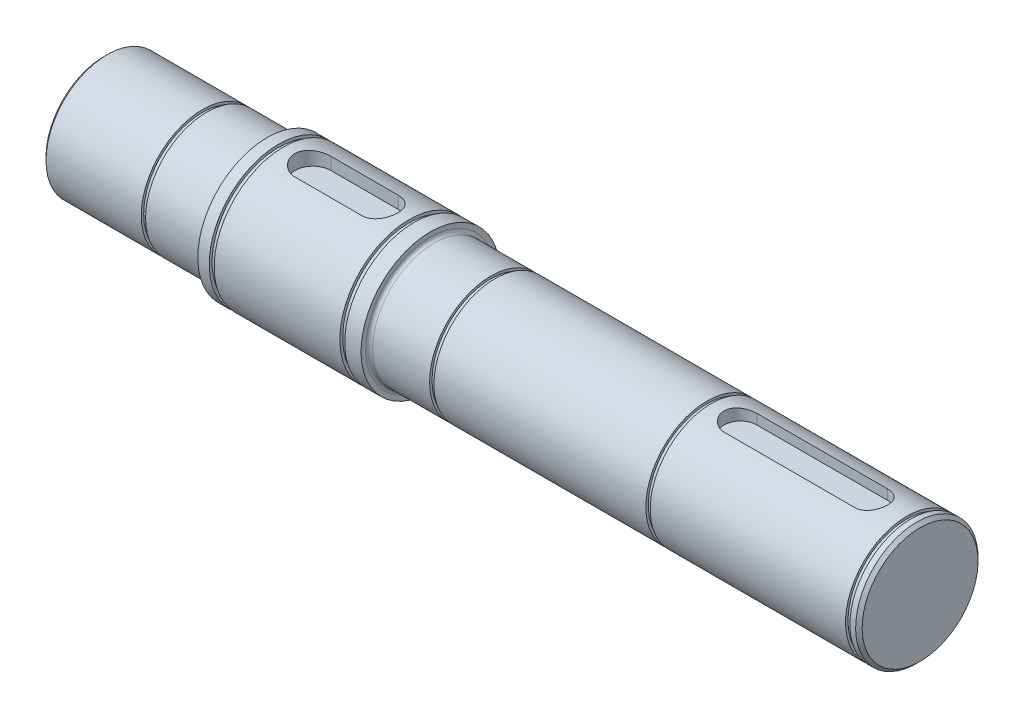
SolidWorks part; units mm, degrees
ref_plane "Front" through (0, 0, 0) normal (0, 0, 1) x (1, 0, 0)
ref_plane "Top" through (0, 0, 0) normal (0, 1, 0) x (1, 0, 0)
ref_plane "Right" through (0, 0, 0) normal (1, 0, 0) x (0, 0, -1)
sketch "Esquisse1" plane through (0, 0, 0) normal (0, 0, 1) x (1, 0, 0)
  line L0 (0, 0) -> (0, 37.5)
  line L1 (0, 37.5) -> (97.9, 37.5)
  line L3 (100, 42.5) -> (200, 42.5)
  line L5 (202.1, 37.5) -> (500, 37.5)
  line L6 (500, 37.5) -> (500, 0)
  line L7 (500, 0) -> (0, 0)
  line L8 (100, 42.5) -> (100, 39.6)
  line L9 (200, 42.5) -> (200, 39.6)
  arc A2 (200, 39.6) -> (202.1, 37.5) centre (202.1, 39.6) ccw
  arc A3 (100, 39.6) -> (97.9, 37.5) centre (97.9, 39.6) cw
  point P3 (200.5198, 37.5)
  dimension "D4" = 2.1
  dimension "D1" = 37.5
  dimension "D2" = 100
  dimension "D3" = 500
  dimension "D5" = 42.5
  dimension "D7" = 100
revolve "Révolution1" add sketch "Esquisse1" angle 360 about L7
ref_plane "Plan1" through (110, 0, 0) normal (1, 0, 0) x (0, 0, -1)
ref_plane "Plan2" through (190, 0, 0) normal (1, 0, 0) x (0, 0, -1)
sketch "Esquisse2" plane through (110, 0, 0) normal (1, 0, 0) x (0, 0, -1)
  circle A2 centre (0, 0) radius 42.5
  circle A3 centre (0, 0) radius 40.75
  dimension "D1" = 1.75
extrude "Enlèv. mat.-Extru.1" cut sketch "Esquisse2" against normal blind 3
sketch "Esquisse3" plane through (190, 0, 0) normal (1, 0, 0) x (0, 0, -1)
  circle A1 centre (0, 0) radius 42.5
  circle A2 centre (0, 0) radius 40.75
  dimension "D1" = 1.75
extrude "Enlèv. mat.-Extru.2" cut sketch "Esquisse3" against normal blind 3
ref_plane "Plan3" through (0, 42.5, 0) normal (0, 1, 0) x (1, 0, 0)
sketch "Esquisse4" plane through (0, 42.5, 0) normal (0, 1, 0) x (1, 0, 0)
  line L0 (148.5, 42.5) -> (148.5, 0) construction
  line L1 (187, 42.5) -> (110, 42.5) construction
  line L2 (128, 0) -> (169, 0) construction
  line L3 (128, 11) -> (169, 11)
  line L4 (128, -11) -> (169, -11)
  arc A0 (128, 11) -> (128, -11) centre (128, 0) ccw
  arc A1 (169, -11) -> (169, 11) centre (169, 0) ccw
  point P6 (148.5, 0)
  dimension "D2" = 11
  dimension "D1" = 41
extrude "Enlèv. mat.-Extru.3" cut sketch "Esquisse4" against normal blind 9
ref_plane "Plan4" through (0, 37.5, 0) normal (0, 1, 0) x (1, 0, 0)
sketch "Esquisse5" plane through (0, 37.5, 0) normal (0, 1, 0) x (1, 0, 0)
  line L0 (500, 0) -> (430, 0) construction
  line L1 (500, -37.5) -> (500, 37.5) construction
  line L2 (470, 0) -> (390, 0) construction
  line L3 (470, -10) -> (390, -10)
  line L4 (470, 10) -> (390, 10)
  arc A0 (470, -10) -> (470, 10) centre (470, 0) ccw
  arc A1 (390, 10) -> (390, -10) centre (390, 0) ccw
  point P7 (430, 0)
  dimension "D2" = 10
  dimension "D1" = 70
  dimension "D3" = 80
extrude "Enlèv. mat.-Extru.4" cut sketch "Esquisse5" against normal blind 7.5
chamfer "Chanfrein1" distance 2 angle 45 2 edges at (500, 37.5, 0) (0, 37.5, 0)
ref_plane "Plan5" through (494.5, 0, 0) normal (1, 0, 0) x (0, 0, -1)
sketch "Esquisse6" plane through (494.5, 0, 0) normal (1, 0, 0) x (0, 0, -1)
  circle A0 centre (0, 0) radius 37.5 construction
  circle A1 centre (0, 0) radius 37.5
  circle A2 centre (0, 0) radius 36
  dimension "D1" = 1.5
extrude "Enlèv. mat.-Extru.5" cut sketch "Esquisse6" against normal blind 2.65
ref_plane "Plan6" through (60.35, 0, 0) normal (-1, 0, 0) x (0, 0, 1)
sketch "Esquisse7" plane through (60.35, 0, 0) normal (-1, 0, 0) x (0, 0, 1)
  circle A0 centre (0, 0) radius 37.5 construction
  circle A1 centre (0, 0) radius 37.5
  circle A2 centre (0, 0) radius 36
  dimension "D1" = 1.5
extrude "Enlèv. mat.-Extru.6" cut sketch "Esquisse7" against normal blind 2.65
ref_plane "Plan8" through (239.65, 0, 0) normal (-1, 0, 0) x (0, 0, 1)
sketch "Esquisse8" plane through (239.65, 0, 0) normal (-1, 0, 0) x (0, 0, 1)
  circle A0 centre (0, 0) radius 37.5 construction
  circle A1 centre (0, 0) radius 37.5
  circle A2 centre (0, 0) radius 36
  dimension "D1" = 1.5
extrude "Enlèv. mat.-Extru.7" cut sketch "Esquisse8" along normal blind 2.65
ref_plane "Plan9" through (369.5, 0, 0) normal (1, 0, 0) x (0, 0, -1)
sketch "Esquisse10" plane through (369.5, 0, 0) normal (1, 0, 0) x (0, 0, -1)
  circle A1 centre (0, 0) radius 37.5
  circle A2 centre (0, 0) radius 36
  dimension "D1" = 1.5
extrude "Enlèv. mat.-Extru.11" cut sketch "Esquisse10" along normal blind 2.65
